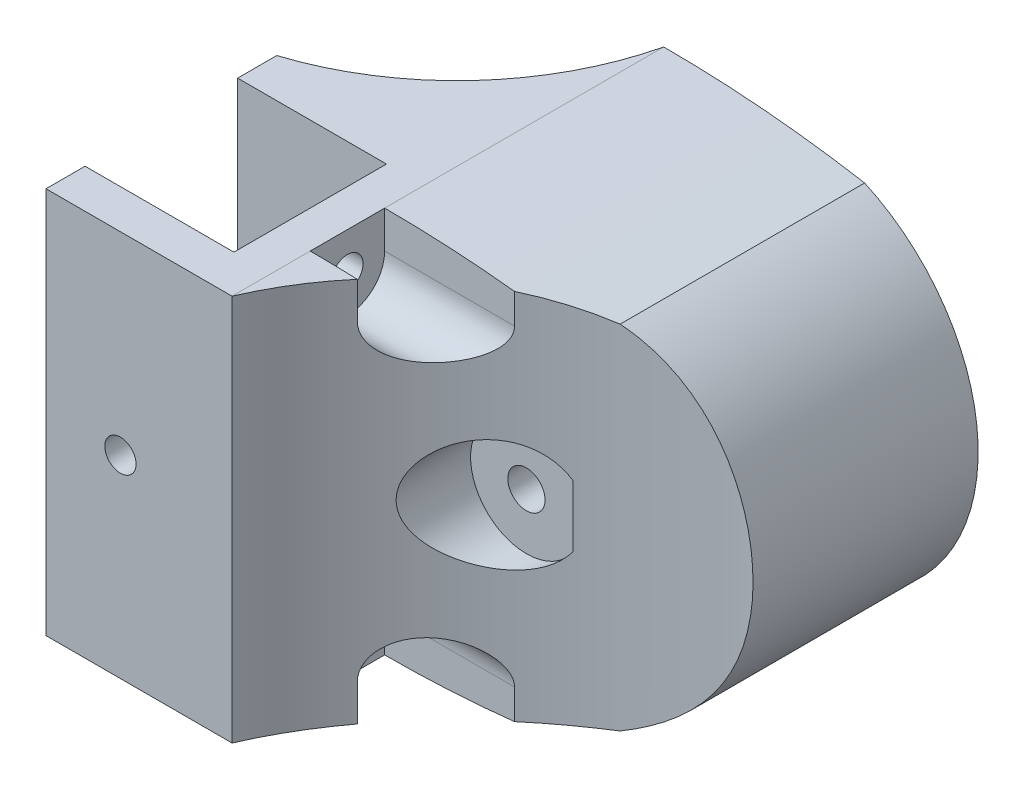
SolidWorks part; units mm, degrees
material "PBT Общее назначение"
ref_plane "Спереди" through (0, 0, 0) normal (0, 0, 1) x (1, 0, 0)
ref_plane "Сверху" through (0, 0, 0) normal (0, 1, 0) x (1, 0, 0)
ref_plane "Справа" through (0, 0, 0) normal (1, 0, 0) x (0, 0, -1)
sketch "Эскиз1" plane through (0, 0, 0) normal (0, 0, 1) x (1, 0, 0)
  line L0 (0, 0) -> (61.556, 0) construction
  line L1 (0, 26) -> (0, -26)
  line L2 (0, 26) -> (52, 26)
  line L3 (0, -26) -> (52, -26)
  line L4 (52, 26) -> (52, -26)
  line L5 (0, 0) -> (52, 0) construction
  dimension "D1" = 52
  dimension "D2" = 52
extrude "Бобышка-Вытянуть1" add sketch "Эскиз1" along normal blind 31
sketch "Эскиз2" plane through (0, 0, 0) normal (-1, 0, 0) x (0, 0, 1)
  line L0 (15.5, 26) -> (15.5, -26) construction
  line L1 (31, 26) -> (0, 26) construction
  line L2 (31, -26) -> (0, -26) construction
  line L3 (5.25, 26) -> (25.75, 26)
  line L4 (5.25, 26) -> (5.25, -26)
  line L5 (25.75, 26) -> (25.75, -26)
  line L6 (5.25, -26) -> (25.75, -26)
  line L7 (15.5, 26) -> (15.5, -26) construction
  dimension "D1" = 20.5
extrude "Вырез-Вытянуть1" cut sketch "Эскиз2" against normal blind 20
sketch "Эскиз3" plane through (52, 0, 0) normal (1, 0, 0) x (0, 0, -1)
  line L0 (-15.5, 26) -> (-15.5, -26) construction
  line L1 (-31, 26) -> (0, 26) construction
  line L2 (-31, -26) -> (0, -26) construction
  line L3 (-31, 0) -> (0, 0) construction
  line L4 (-31, -26) -> (-31, 26) construction
  line L5 (0, -26) -> (0, 26) construction
ref_plane "СимZ" through (0, 0, 15.5) normal (0, 0, 1) x (0, -1, 0)
ref_plane "СимY" through (0, 0, 0) normal (0, -1, 0) x (0, 0, -1)
sketch "Эскиз4" plane through (0, 26, 0) normal (0, 1, 0) x (1, 0, 0)
  line L0 (41.25, 0) -> (41.25, -31) construction
  line L1 (52, 0) -> (0, 0) construction
  line L2 (52, -31) -> (0, -31) construction
  line L3 (20, -25.75) -> (20, -5.25) construction
  line L4 (20, -25.75) -> (20, -5.25) construction
  dimension "D1" = 21.25
ref_plane "Симм Лента" through (41.25, 0, 0) normal (-1, 0, 0) x (0, 0, 1)
sketch "Эскиз5" plane through (0, 0, 31) normal (0, 0, 1) x (1, 0, 0)
  line L0 (41.25, 26) -> (41.25, -26) construction
  line L1 (0, -26) -> (52, -26) construction
  line L2 (52, 26) -> (0, 26) construction
  circle A0 centre (41.25, 0) radius 26
extrude "Бобышка-Вытянуть2" add sketch "Эскиз5" against normal up to surface (31 mm away) up to face at (26, 0, 0)
sketch "Эскиз6" plane through (0, 0, 31) normal (0, 0, 1) x (1, 0, 0)
  line L2 (52, 23.6736) -> (52, 26) construction
  line L3 (52, 26) -> (0, 26) construction
  line L4 (52, 23.6736) -> (52, 26)
  line L5 (52, 26) -> (25, 26)
  arc A0 (52, 23.6736) -> (25, 26) centre (25, -131.8405) ccw
  dimension "D1" = 25
extrude "Вырез-Вытянуть2" cut sketch "Эскиз6" against normal through all
mirror "Зеркальное отражение1" about plane through (0, 0, 0) normal (0, -1, 0) of "Вырез-Вытянуть2"
sketch "Эскиз7" plane through (0, 26, 0) normal (0, 1, 0) x (1, 0, 0)
  line L0 (20, -25.75) -> (20, -5.25) construction
  line L1 (20, -25.75) -> (0, -25.75) construction
  line L2 (20, -5.25) -> (0, -5.25) construction
  line L3 (20, -25.75) -> (20, -5.25)
  line L4 (20, -25.75) -> (0, -25.75)
  line L5 (20, -5.25) -> (0, -5.25)
  line L6 (0, -5.25) -> (0, -25.75)
extrude "Вырез-Вытянуть3" cut sketch "Эскиз7" against normal through all
sketch "Эскиз8" plane through (0, 26, 0) normal (0, 1, 0) x (1, 0, 0)
  line L0 (35.2, 15.75) -> (47.3, 15.75) construction
  line L1 (35.2, 15.75) -> (47.3, 15.75) construction
  line L2 (47.3, 8.35) -> (35.2, 8.35) construction
  line L3 (47.3, 8.35) -> (35.2, 8.35) construction
  line L4 (25, 0) -> (0, 0) construction
  dimension "D1" = 8.35
  dimension "D2" = 15.75
sketch "Эскиз9" plane through (0, 0, 0) normal (0, 0, -1) x (-1, 0, 0)
  line L0 (-25, 26) -> (-25, -26)
  arc A0 (-25, 26) -> (-52, 23.6736) centre (-25, -131.8405) ccw construction
  arc A1 (-52, 23.6736) -> (-52, -23.6736) centre (-41.25, 0) ccw construction
  arc A2 (-52, -23.6736) -> (-25, -26) centre (-25, 131.8405) ccw construction
  arc A3 (-25, 26) -> (-52, 23.6736) centre (-25, -131.8405) ccw
  arc A4 (-52, 23.6736) -> (-52, -23.6736) centre (-41.25, 0) ccw
  arc A5 (-52, -23.6736) -> (-25, -26) centre (-25, 131.8405) ccw
extrude "Бобышка-Вытянуть3" add sketch "Эскиз9" along normal blind 27
sketch "Эскиз10" plane through (41.25, 0, 0) normal (-1, 0, 0) x (0, 0, 1)
  line L0 (0, -26) -> (0, 26) construction
  line L1 (0, -26) -> (0, 26) construction
  line L2 (-6.75, 9) -> (-15.75, 9) construction
  line L3 (-6.75, 9) -> (-6.75, -9) construction
  line L4 (-15.75, 9) -> (-15.75, -9) construction
  line L5 (-6.75, -9) -> (-15.75, -9) construction
  line L6 (-15.75, 0) -> (-6.75, 0) construction
  line L7 (-27, -26) -> (-27, 26) construction
  line L8 (-27, -26) -> (-27, 26) construction
  line L9 (-27, 0) -> (0, 0) construction
  line L10 (-11.25, 9) -> (-11.25, -9) construction
  line L11 (-20.75, 14) -> (-1.75, 14)
  line L12 (-20.75, 14) -> (-20.75, 0)
  line L13 (-20.75, 0) -> (-1.75, 0)
  line L14 (-1.75, 0) -> (-1.75, 14)
  dimension "D1" = 15.75
  dimension "D2" = 9
  dimension "D3" = 18
  dimension "D4" = 5
  dimension "D5" = 5
  dimension "D6" = 5
revolve "Вырез-Повернуть2" cut sketch "Эскиз10" angle 360 about L13
sketch "Эскиз11" plane through (0, 0, 0) normal (0, -1, 0) x (0, 0, -1)
  line L0 (1.75, 27.25) -> (1.75, 55.25) construction
  line L1 (1.75, 27.25) -> (1.75, 55.25)
  line L2 (20.75, 55.25) -> (20.75, 27.25) construction
  line L3 (20.75, 55.25) -> (20.75, 27.25)
  line L4 (20.75, 55.25) -> (1.75, 55.25)
  line L5 (20.75, 27.25) -> (1.75, 27.25)
extrude "Вырез-Вытянуть4" cut sketch "Эскиз11" along normal through all
sketch "Эскиз12" plane through (0, -26, 0) normal (0, -1, 0) x (1, 0, 0)
  line L0 (0, 0) -> (25, 0) construction
  line L1 (25, -27) -> (25, 0) construction
  line L2 (0, 0) -> (25, 0)
  line L3 (25, -27) -> (25, 0)
  arc A0 (25, -27) -> (0, 0) centre (-11.4767, -35.7006) ccw
  dimension "D1" = 75
extrude "Бобышка-Вытянуть4" add sketch "Эскиз12" against normal up to surface (52 mm away) up to face at (11.25, 26, 15.5)
sketch "Эскиз13" plane through (0, 0, 31) normal (0, 0, 1) x (1, 0, 0)
  line L0 (10, -26) -> (10, 26) construction
  line L4 (20, 26) -> (0, 26)
  line L5 (20, -26) -> (20, 26)
  line L6 (0, -26) -> (20, -26)
  line L7 (0, 26) -> (0, -26)
  line L8 (20, 26) -> (0, 26) construction
  line L9 (20, -26) -> (20, 26) construction
  line L10 (0, -26) -> (20, -26) construction
  line L11 (0, 26) -> (0, -26) construction
  circle A0 centre (10, 0) radius 2.1
  dimension "D2" = 4.2
  dimension "D1" = 0
extrude "Вырез-Вытянуть5" cut sketch "Эскиз13" against normal through all
sketch "Эскиз14" plane through (20, 0, 0) normal (-1, 0, 0) x (0, 0, 1)
  line L0 (15.5, -26) -> (15.5, 26) construction
  line L4 (5.25, 26) -> (5.25, -26)
  line L5 (5.25, -26) -> (25.75, -26)
  line L6 (25.75, -26) -> (25.75, 26)
  line L7 (25.75, 26) -> (5.25, 26)
  line L8 (5.25, 26) -> (5.25, -26) construction
  line L9 (5.25, -26) -> (25.75, -26) construction
  line L10 (25.75, -26) -> (25.75, 26) construction
  line L11 (25.75, 26) -> (5.25, 26) construction
  circle A0 centre (15.5, -21) radius 2.1
  circle A1 centre (15.5, 21) radius 2.1
  dimension "D2" = 5
  dimension "D3" = 4.2
  dimension "D4" = 4.2
  dimension "D5" = 5
  dimension "D1" = 0
extrude "Вырез-Вытянуть6" cut sketch "Эскиз14" against normal through all
ref_plane "Плоскость1" through (25, 0, 0) normal (1, 0, 0) x (0, 0, -1)
sketch "Эскиз15" plane through (25, 0, 0) normal (1, 0, 0) x (0, 0, -1)
  circle A0 centre (-15.5, 21) radius 2.1 construction
  circle A1 centre (-15.5, 21) radius 2.1 construction
  circle A2 centre (-15.5, -21) radius 2.1 construction
  circle A3 centre (-15.5, -21) radius 2.1 construction
  circle A4 centre (-15.5, 21) radius 5
  circle A5 centre (-15.5, -21) radius 5
  dimension "D1" = 10
  dimension "D2" = 10
extrude "Вырез-Вытянуть7" cut sketch "Эскиз15" along normal through all
sketch "Эскиз16" plane through (20, 0, 0) normal (-1, 0, 0) x (0, 0, 1)
  line L0 (17.6, 21) -> (13.4, 21) construction
  circle A0 centre (15.5, 21) radius 2.1 construction
ref_plane "Плоскость2" through (0, 21, 0) normal (0, 1, 0) x (0, 0, -1)
sketch "Эскиз17" plane through (0, 21, 0) normal (0, 1, 0) x (0, 0, -1)
  line L0 (-20.5, -25) -> (-10.5, -25) construction
  line L1 (-20.5, -25) -> (-10.5, -25)
  line L2 (-10.5, -25) -> (-10.5, -67.25)
  line L3 (-20.5, -25) -> (-20.5, -67.25)
  line L5 (27, -67.25) -> (27, -52) construction
  line L6 (27, -67.25) -> (27, -52) construction
  line L7 (-10.5, -67.25) -> (-20.5, -67.25)
  line L8 (27, -67.25) -> (-10.5, -67.25) construction
extrude "Вырез-Вытянуть8" cut sketch "Эскиз17" along normal through all
mirror "Зеркальное отражение2" about plane through (0, 0, 0) normal (0, -1, 0) of "Вырез-Вытянуть8"
ref_plane "Плоскость3" through (0, 0, 0) normal (0, 0, -1) x (-1, 0, 0)
sketch "Эскиз18" plane through (0, 0, 0) normal (0, 0, -1) x (-1, 0, 0)
  circle A0 centre (-10, 0) radius 2.1 construction
  circle A1 centre (-10, 0) radius 2.1 construction
  circle A2 centre (-10, 0) radius 5
  dimension "D1" = 10
extrude "Вырез-Вытянуть9" cut sketch "Эскиз18" along normal through all
sketch "Эскиз19" plane through (0, 0, 31) normal (0, 0, 1) x (1, 0, 0)
  arc A0 (52, -23.6736) -> (52, 23.6736) centre (41.25, 0) ccw construction
  arc A1 (52, -23.6736) -> (52, 23.6736) centre (41.25, 0) ccw construction
  circle A2 centre (41.25, 0) radius 26 construction
  circle A3 centre (41.25, 0) radius 2.5
  dimension "D1" = 5
extrude "Вырез-Вытянуть10" cut sketch "Эскиз19" against normal through all
sketch "Sketch1" plane through (0, 26, 0) normal (0, 1, 0) x (1, 0, 0)
  line L14 (67.25, 27) -> (52, 27) construction
  line L15 (67.25, 27) -> (52, 27) construction
  line L16 (52, -31) -> (67.25, -31) construction
  line L17 (25, -31) -> (67.25, -31)
  line L18 (67.25, -31) -> (67.25, -3.25)
  line L19 (52, 1.75) -> (27.25, 1.75) construction
  line L20 (52, 1.75) -> (27.25, 1.75) construction
  line L21 (28.1092, -3.25) -> (67.25, -3.25) construction
  line L23 (67.25, -3.25) -> (67.25, 27) construction
  arc A0 (67.25, -3.25) -> (25, -31) centre (67.25, -49.2883) ccw
  point P10 (67.25, -3.25)
  dimension "D2" = 5
extrude "Cut-Extrude1" cut sketch "Sketch1" against normal through all
sketch "Sketch2" plane through (0, 0, 0) normal (0, -1, 0) x (0, 0, -1)
  line L0 (-9.6995, 43.75) -> (-9.6995, -35.6568) construction
  line L1 (20.75, 43.75) -> (20.75, 38.75) construction
  line L2 (20.75, 43.75) -> (20.75, 38.75) construction
  line L3 (20.75, 41.25) -> (-31.3718, 41.25) construction
  arc A0 (-13.132, 38.75) -> (-9.6995, 43.75) centre (-49.2883, 67.25) ccw construction
  arc A1 (-13.132, 38.75) -> (-9.6995, 43.75) centre (-49.2883, 67.25) ccw construction
ref_plane "Plane1" through (0, 0, 9.6995) normal (0, 0, 1) x (1, 0, 0)
sketch "Sketch3" plane through (0, 0, 9.6995) normal (0, 0, 1) x (1, 0, 0)
  circle A0 centre (41.25, 0) radius 2.5 construction
  circle A1 centre (41.25, 0) radius 2.5 construction
  circle A2 centre (41.25, 0) radius 7.5
  dimension "D1" = 15
extrude "Cut-Extrude2" cut sketch "Sketch3" along normal through all and the other way blind 2
